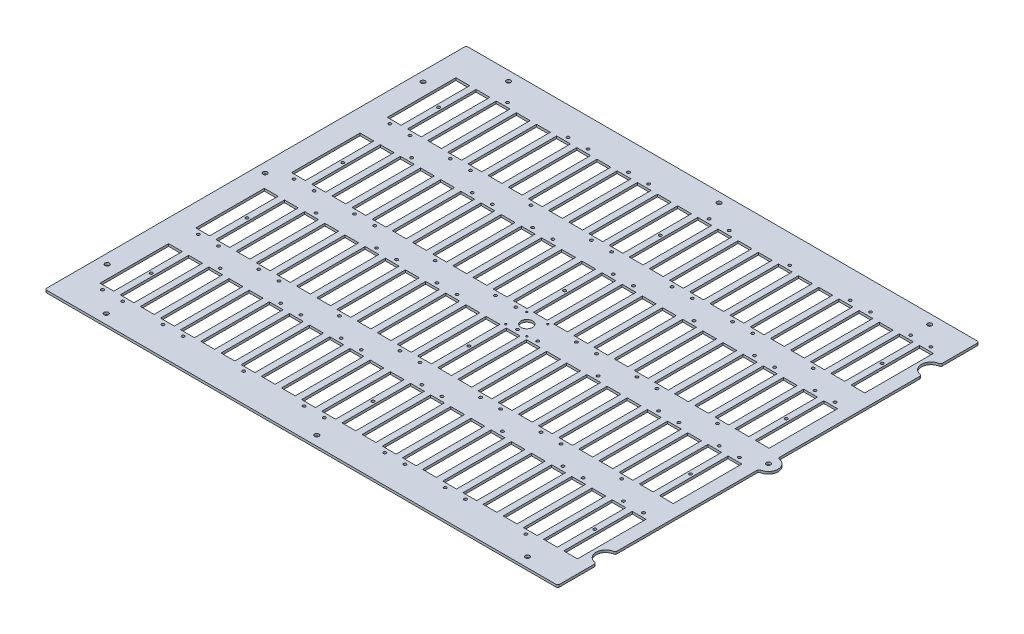
SolidWorks part; units mm, degrees
ref_plane "Front Plane" through (0, 0, 0) normal (0, 0, 1) x (1, 0, 0)
ref_plane "Top Plane" through (0, 0, 0) normal (0, 1, 0) x (1, 0, 0)
ref_plane "Right Plane" through (0, 0, 0) normal (1, 0, 0) x (0, 0, -1)
sketch "Sketch1" plane through (0, 0, 0) normal (0, 1, 0) x (1, 0, 0)
  line L0 (340.2584, 228.6) -> (340.2584, 279.5524)
  line L1 (-340.2584, -279.5524) -> (340.2584, -279.5524)
  line L2 (-340.2584, -279.5524) -> (-340.2584, 279.5524)
  line L3 (-340.2584, 279.5524) -> (340.2584, 279.5524)
  line L4 (340.2584, -279.5524) -> (340.2584, -228.6)
  line L5 (-340.2584, -279.5524) -> (340.2584, 279.5524) construction
  line L6 (-340.2584, 279.5524) -> (340.2584, -279.5524) construction
  line L7 (340.2584, 12.7) -> (340.2584, 203.2)
  line L8 (340.2584, -203.2) -> (340.2584, -12.7)
  arc A3 (340.2584, -203.2) -> (340.2584, -228.6) centre (340.2584, -215.9) ccw
  arc A4 (340.2584, -12.7) -> (340.2584, 12.7) centre (340.2584, 0) ccw
  arc A5 (340.2584, 228.6) -> (340.2584, 203.2) centre (340.2584, 215.9) ccw
  point P0 (0, 0)
  dimension "D3" = 25.4
  dimension "D1" = 559.1048
  dimension "D2" = 680.5168
extrude "Boss-Extrude1" add sketch "Sketch1" along normal blind 3.175
sketch "Sketch17" plane through (0, 3.175, 0) normal (0, 1, 0) x (1, 0, 0)
  line L0 (340.2584, 279.5524) -> (-340.2584, 279.5524) construction
  line L1 (-314.8584, 254.1524) -> (327.5584, 254.1524) construction
  line L2 (-314.8584, 254.1524) -> (-314.8584, -254.1524) construction
  line L3 (-314.8584, -254.1524) -> (327.5584, -254.1524) construction
  line L4 (327.5584, 254.1524) -> (327.5584, -254.1524) construction
  line L5 (-340.2584, 279.5524) -> (-340.2584, -279.5524) construction
  line L6 (-340.2584, -279.5524) -> (340.2584, -279.5524) construction
  line L7 (340.2584, -203.2) -> (340.2584, -12.7) construction
  line L8 (-283.8406, 236.1184) -> (-265.5526, 236.1184)
  line L9 (-310.5912, 236.1184) -> (-292.3032, 236.1184)
  line L10 (-310.5912, 236.1184) -> (-310.5912, 145.1864)
  line L11 (-310.5912, 145.1864) -> (-292.3032, 145.1864)
  line L12 (-292.3032, 236.1184) -> (-292.3032, 145.1864)
  line L13 (-283.8406, 236.1184) -> (-283.8406, 145.1864)
  line L14 (-265.5526, 236.1184) -> (-265.5526, 145.1864)
  line L15 (-283.8406, 145.1864) -> (-265.5526, 145.1864)
  line L16 (-257.09, 236.1184) -> (-238.802, 236.1184)
  line L17 (-257.09, 236.1184) -> (-257.09, 145.1864)
  line L18 (-238.802, 236.1184) -> (-238.802, 145.1864)
  line L19 (-257.09, 145.1864) -> (-238.802, 145.1864)
  line L20 (-230.3393, 236.1184) -> (-212.0513, 236.1184)
  line L21 (-230.3393, 236.1184) -> (-230.3393, 145.1864)
  line L22 (-212.0513, 236.1184) -> (-212.0513, 145.1864)
  line L23 (-230.3393, 145.1864) -> (-212.0513, 145.1864)
  line L24 (-203.5887, 236.1184) -> (-185.3007, 236.1184)
  line L25 (-203.5887, 236.1184) -> (-203.5887, 145.1864)
  line L26 (-185.3007, 236.1184) -> (-185.3007, 145.1864)
  line L27 (-203.5887, 145.1864) -> (-185.3007, 145.1864)
  line L28 (-176.8381, 236.1184) -> (-158.5501, 236.1184)
  line L29 (-176.8381, 236.1184) -> (-176.8381, 145.1864)
  line L30 (-158.5501, 236.1184) -> (-158.5501, 145.1864)
  line L31 (-176.8381, 145.1864) -> (-158.5501, 145.1864)
  line L32 (-150.0875, 236.1184) -> (-131.7995, 236.1184)
  line L33 (-150.0875, 236.1184) -> (-150.0875, 145.1864)
  line L34 (-131.7995, 236.1184) -> (-131.7995, 145.1864)
  line L35 (-150.0875, 145.1864) -> (-131.7995, 145.1864)
  line L36 (-123.3369, 236.1184) -> (-105.0489, 236.1184)
  line L37 (-123.3369, 236.1184) -> (-123.3369, 145.1864)
  line L38 (-105.0489, 236.1184) -> (-105.0489, 145.1864)
  line L39 (-123.3369, 145.1864) -> (-105.0489, 145.1864)
  line L40 (-96.5863, 236.1184) -> (-78.2983, 236.1184)
  line L41 (-96.5863, 236.1184) -> (-96.5863, 145.1864)
  line L42 (-78.2983, 236.1184) -> (-78.2983, 145.1864)
  line L43 (-96.5863, 145.1864) -> (-78.2983, 145.1864)
  line L44 (-69.8356, 236.1184) -> (-51.5476, 236.1184)
  line L45 (-69.8356, 236.1184) -> (-69.8356, 145.1864)
  line L46 (-51.5476, 236.1184) -> (-51.5476, 145.1864)
  line L47 (-69.8356, 145.1864) -> (-51.5476, 145.1864)
  line L48 (-43.085, 236.1184) -> (-24.797, 236.1184)
  line L49 (-43.085, 236.1184) -> (-43.085, 145.1864)
  line L50 (-24.797, 236.1184) -> (-24.797, 145.1864)
  line L51 (-43.085, 145.1864) -> (-24.797, 145.1864)
  line L52 (-16.3344, 236.1184) -> (1.9536, 236.1184)
  line L53 (-16.3344, 236.1184) -> (-16.3344, 145.1864)
  line L54 (1.9536, 236.1184) -> (1.9536, 145.1864)
  line L55 (-16.3344, 145.1864) -> (1.9536, 145.1864)
  line L56 (10.4162, 236.1184) -> (28.7042, 236.1184)
  line L57 (10.4162, 236.1184) -> (10.4162, 145.1864)
  line L58 (28.7042, 236.1184) -> (28.7042, 145.1864)
  line L59 (10.4162, 145.1864) -> (28.7042, 145.1864)
  line L60 (37.1668, 236.1184) -> (55.4548, 236.1184)
  line L61 (37.1668, 236.1184) -> (37.1668, 145.1864)
  line L62 (55.4548, 236.1184) -> (55.4548, 145.1864)
  line L63 (37.1668, 145.1864) -> (55.4548, 145.1864)
  line L64 (63.9174, 236.1184) -> (82.2054, 236.1184)
  line L65 (63.9174, 236.1184) -> (63.9174, 145.1864)
  line L66 (82.2054, 236.1184) -> (82.2054, 145.1864)
  line L67 (63.9174, 145.1864) -> (82.2054, 145.1864)
  line L68 (90.6681, 236.1184) -> (108.9561, 236.1184)
  line L69 (90.6681, 236.1184) -> (90.6681, 145.1864)
  line L70 (108.9561, 236.1184) -> (108.9561, 145.1864)
  line L71 (90.6681, 145.1864) -> (108.9561, 145.1864)
  line L72 (117.4187, 236.1184) -> (135.7067, 236.1184)
  line L73 (117.4187, 236.1184) -> (117.4187, 145.1864)
  line L74 (135.7067, 236.1184) -> (135.7067, 145.1864)
  line L75 (117.4187, 145.1864) -> (135.7067, 145.1864)
  line L76 (144.1693, 236.1184) -> (162.4573, 236.1184)
  line L77 (144.1693, 236.1184) -> (144.1693, 145.1864)
  line L78 (162.4573, 236.1184) -> (162.4573, 145.1864)
  line L79 (144.1693, 145.1864) -> (162.4573, 145.1864)
  line L80 (170.9199, 236.1184) -> (189.2079, 236.1184)
  line L81 (170.9199, 236.1184) -> (170.9199, 145.1864)
  line L82 (189.2079, 236.1184) -> (189.2079, 145.1864)
  line L83 (170.9199, 145.1864) -> (189.2079, 145.1864)
  line L84 (197.6705, 236.1184) -> (215.9585, 236.1184)
  line L85 (197.6705, 236.1184) -> (197.6705, 145.1864)
  line L86 (215.9585, 236.1184) -> (215.9585, 145.1864)
  line L87 (197.6705, 145.1864) -> (215.9585, 145.1864)
  line L88 (224.4211, 236.1184) -> (242.7091, 236.1184)
  line L89 (224.4211, 236.1184) -> (224.4211, 145.1864)
  line L90 (242.7091, 236.1184) -> (242.7091, 145.1864)
  line L91 (224.4211, 145.1864) -> (242.7091, 145.1864)
  line L92 (251.1718, 236.1184) -> (269.4598, 236.1184)
  line L93 (251.1718, 236.1184) -> (251.1718, 145.1864)
  line L94 (269.4598, 236.1184) -> (269.4598, 145.1864)
  line L95 (251.1718, 145.1864) -> (269.4598, 145.1864)
  line L96 (277.9224, 236.1184) -> (296.2104, 236.1184)
  line L97 (277.9224, 236.1184) -> (277.9224, 145.1864)
  line L98 (296.2104, 236.1184) -> (296.2104, 145.1864)
  line L99 (277.9224, 145.1864) -> (296.2104, 145.1864)
  line L100 (304.673, 236.1184) -> (322.961, 236.1184)
  line L101 (304.673, 236.1184) -> (304.673, 145.1864)
  line L102 (322.961, 236.1184) -> (322.961, 145.1864)
  line L103 (304.673, 145.1864) -> (322.961, 145.1864)
  line L104 (-283.8406, 109.0422) -> (-265.5526, 109.0422)
  line L105 (-283.8406, 109.0422) -> (-283.8406, 18.1102)
  line L106 (-265.5526, 109.0422) -> (-265.5526, 18.1102)
  line L107 (-283.8406, 18.1102) -> (-265.5526, 18.1102)
  line L108 (-257.09, 109.0422) -> (-238.802, 109.0422)
  line L109 (-257.09, 109.0422) -> (-257.09, 18.1102)
  line L110 (-238.802, 109.0422) -> (-238.802, 18.1102)
  line L111 (-257.09, 18.1102) -> (-238.802, 18.1102)
  line L112 (-230.3393, 109.0422) -> (-212.0513, 109.0422)
  line L113 (-230.3393, 109.0422) -> (-230.3393, 18.1102)
  line L114 (-212.0513, 109.0422) -> (-212.0513, 18.1102)
  line L115 (-230.3393, 18.1102) -> (-212.0513, 18.1102)
  line L116 (-203.5887, 109.0422) -> (-185.3007, 109.0422)
  line L117 (-203.5887, 109.0422) -> (-203.5887, 18.1102)
  line L118 (-185.3007, 109.0422) -> (-185.3007, 18.1102)
  line L119 (-203.5887, 18.1102) -> (-185.3007, 18.1102)
  line L120 (-176.8381, 109.0422) -> (-158.5501, 109.0422)
  line L121 (-176.8381, 109.0422) -> (-176.8381, 18.1102)
  line L122 (-158.5501, 109.0422) -> (-158.5501, 18.1102)
  line L123 (-176.8381, 18.1102) -> (-158.5501, 18.1102)
  line L124 (-150.0875, 109.0422) -> (-131.7995, 109.0422)
  line L125 (-150.0875, 109.0422) -> (-150.0875, 18.1102)
  line L126 (-131.7995, 109.0422) -> (-131.7995, 18.1102)
  line L127 (-150.0875, 18.1102) -> (-131.7995, 18.1102)
  line L128 (-123.3369, 109.0422) -> (-105.0489, 109.0422)
  line L129 (-123.3369, 109.0422) -> (-123.3369, 18.1102)
  line L130 (-105.0489, 109.0422) -> (-105.0489, 18.1102)
  line L131 (-123.3369, 18.1102) -> (-105.0489, 18.1102)
  line L132 (-96.5863, 109.0422) -> (-78.2983, 109.0422)
  line L133 (-96.5863, 109.0422) -> (-96.5863, 18.1102)
  line L134 (-78.2983, 109.0422) -> (-78.2983, 18.1102)
  line L135 (-96.5863, 18.1102) -> (-78.2983, 18.1102)
  line L136 (-69.8356, 109.0422) -> (-51.5476, 109.0422)
  line L137 (-69.8356, 109.0422) -> (-69.8356, 18.1102)
  line L138 (-51.5476, 109.0422) -> (-51.5476, 18.1102)
  line L139 (-69.8356, 18.1102) -> (-51.5476, 18.1102)
  line L140 (-43.085, 109.0422) -> (-24.797, 109.0422)
  line L141 (-43.085, 109.0422) -> (-43.085, 18.1102)
  line L142 (-24.797, 109.0422) -> (-24.797, 18.1102)
  line L143 (-43.085, 18.1102) -> (-24.797, 18.1102)
  line L144 (-16.3344, 109.0422) -> (1.9536, 109.0422)
  line L145 (-16.3344, 109.0422) -> (-16.3344, 18.1102)
  line L146 (1.9536, 109.0422) -> (1.9536, 18.1102)
  line L147 (-16.3344, 18.1102) -> (1.9536, 18.1102)
  line L148 (10.4162, 109.0422) -> (28.7042, 109.0422)
  line L149 (10.4162, 109.0422) -> (10.4162, 18.1102)
  line L150 (28.7042, 109.0422) -> (28.7042, 18.1102)
  line L151 (10.4162, 18.1102) -> (28.7042, 18.1102)
  line L152 (37.1668, 109.0422) -> (55.4548, 109.0422)
  line L153 (37.1668, 109.0422) -> (37.1668, 18.1102)
  line L154 (55.4548, 109.0422) -> (55.4548, 18.1102)
  line L155 (37.1668, 18.1102) -> (55.4548, 18.1102)
  line L156 (63.9174, 109.0422) -> (82.2054, 109.0422)
  line L157 (63.9174, 109.0422) -> (63.9174, 18.1102)
  line L158 (82.2054, 109.0422) -> (82.2054, 18.1102)
  line L159 (63.9174, 18.1102) -> (82.2054, 18.1102)
  line L160 (90.6681, 109.0422) -> (108.9561, 109.0422)
  line L161 (90.6681, 109.0422) -> (90.6681, 18.1102)
  line L162 (108.9561, 109.0422) -> (108.9561, 18.1102)
  line L163 (90.6681, 18.1102) -> (108.9561, 18.1102)
  line L164 (117.4187, 109.0422) -> (135.7067, 109.0422)
  line L165 (117.4187, 109.0422) -> (117.4187, 18.1102)
  line L166 (135.7067, 109.0422) -> (135.7067, 18.1102)
  line L167 (117.4187, 18.1102) -> (135.7067, 18.1102)
  line L168 (144.1693, 109.0422) -> (162.4573, 109.0422)
  line L169 (144.1693, 109.0422) -> (144.1693, 18.1102)
  line L170 (162.4573, 109.0422) -> (162.4573, 18.1102)
  line L171 (144.1693, 18.1102) -> (162.4573, 18.1102)
  line L172 (170.9199, 109.0422) -> (189.2079, 109.0422)
  line L173 (170.9199, 109.0422) -> (170.9199, 18.1102)
  line L174 (189.2079, 109.0422) -> (189.2079, 18.1102)
  line L175 (170.9199, 18.1102) -> (189.2079, 18.1102)
  line L176 (197.6705, 109.0422) -> (215.9585, 109.0422)
  line L177 (197.6705, 109.0422) -> (197.6705, 18.1102)
  line L178 (215.9585, 109.0422) -> (215.9585, 18.1102)
  line L179 (197.6705, 18.1102) -> (215.9585, 18.1102)
  line L180 (224.4211, 109.0422) -> (242.7091, 109.0422)
  line L181 (224.4211, 109.0422) -> (224.4211, 18.1102)
  line L182 (242.7091, 109.0422) -> (242.7091, 18.1102)
  line L183 (224.4211, 18.1102) -> (242.7091, 18.1102)
  line L184 (251.1718, 109.0422) -> (269.4598, 109.0422)
  line L185 (251.1718, 109.0422) -> (251.1718, 18.1102)
  line L186 (269.4598, 109.0422) -> (269.4598, 18.1102)
  line L187 (251.1718, 18.1102) -> (269.4598, 18.1102)
  line L188 (277.9224, 109.0422) -> (296.2104, 109.0422)
  line L189 (277.9224, 109.0422) -> (277.9224, 18.1102)
  line L190 (296.2104, 109.0422) -> (296.2104, 18.1102)
  line L191 (277.9224, 18.1102) -> (296.2104, 18.1102)
  line L192 (304.673, 109.0422) -> (322.961, 109.0422)
  line L193 (304.673, 109.0422) -> (304.673, 18.1102)
  line L194 (322.961, 109.0422) -> (322.961, 18.1102)
  line L195 (304.673, 18.1102) -> (322.961, 18.1102)
  line L196 (-283.8406, -18.034) -> (-265.5526, -18.034)
  line L197 (-283.8406, -18.034) -> (-283.8406, -108.966)
  line L198 (-265.5526, -18.034) -> (-265.5526, -108.966)
  line L199 (-283.8406, -108.966) -> (-265.5526, -108.966)
  line L200 (-257.09, -18.034) -> (-238.802, -18.034)
  line L201 (-257.09, -18.034) -> (-257.09, -108.966)
  line L202 (-238.802, -18.034) -> (-238.802, -108.966)
  line L203 (-257.09, -108.966) -> (-238.802, -108.966)
  line L204 (-230.3393, -18.034) -> (-212.0513, -18.034)
  line L205 (-230.3393, -18.034) -> (-230.3393, -108.966)
  line L206 (-212.0513, -18.034) -> (-212.0513, -108.966)
  line L207 (-230.3393, -108.966) -> (-212.0513, -108.966)
  line L208 (-203.5887, -18.034) -> (-185.3007, -18.034)
  line L209 (-203.5887, -18.034) -> (-203.5887, -108.966)
  line L210 (-185.3007, -18.034) -> (-185.3007, -108.966)
  line L211 (-203.5887, -108.966) -> (-185.3007, -108.966)
  line L212 (-176.8381, -18.034) -> (-158.5501, -18.034)
  line L213 (-176.8381, -18.034) -> (-176.8381, -108.966)
  line L214 (-158.5501, -18.034) -> (-158.5501, -108.966)
  line L215 (-176.8381, -108.966) -> (-158.5501, -108.966)
  line L216 (-150.0875, -18.034) -> (-131.7995, -18.034)
  line L217 (-150.0875, -18.034) -> (-150.0875, -108.966)
  line L218 (-131.7995, -18.034) -> (-131.7995, -108.966)
  line L219 (-150.0875, -108.966) -> (-131.7995, -108.966)
  line L220 (-123.3369, -18.034) -> (-105.0489, -18.034)
  line L221 (-123.3369, -18.034) -> (-123.3369, -108.966)
  line L222 (-105.0489, -18.034) -> (-105.0489, -108.966)
  line L223 (-123.3369, -108.966) -> (-105.0489, -108.966)
  line L224 (-96.5863, -18.034) -> (-78.2983, -18.034)
  line L225 (-96.5863, -18.034) -> (-96.5863, -108.966)
  line L226 (-78.2983, -18.034) -> (-78.2983, -108.966)
  line L227 (-96.5863, -108.966) -> (-78.2983, -108.966)
  line L228 (-69.8356, -18.034) -> (-51.5476, -18.034)
  line L229 (-69.8356, -18.034) -> (-69.8356, -108.966)
  line L230 (-51.5476, -18.034) -> (-51.5476, -108.966)
  line L231 (-69.8356, -108.966) -> (-51.5476, -108.966)
  line L232 (-43.085, -18.034) -> (-24.797, -18.034)
  line L233 (-43.085, -18.034) -> (-43.085, -108.966)
  line L234 (-24.797, -18.034) -> (-24.797, -108.966)
  line L235 (-43.085, -108.966) -> (-24.797, -108.966)
  line L236 (-16.3344, -18.034) -> (1.9536, -18.034)
  line L237 (-16.3344, -18.034) -> (-16.3344, -108.966)
  line L238 (1.9536, -18.034) -> (1.9536, -108.966)
  line L239 (-16.3344, -108.966) -> (1.9536, -108.966)
  line L240 (10.4162, -18.034) -> (28.7042, -18.034)
  line L241 (10.4162, -18.034) -> (10.4162, -108.966)
  line L242 (28.7042, -18.034) -> (28.7042, -108.966)
  line L243 (10.4162, -108.966) -> (28.7042, -108.966)
  line L244 (37.1668, -18.034) -> (55.4548, -18.034)
  line L245 (37.1668, -18.034) -> (37.1668, -108.966)
  line L246 (55.4548, -18.034) -> (55.4548, -108.966)
  line L247 (37.1668, -108.966) -> (55.4548, -108.966)
  line L248 (63.9174, -18.034) -> (82.2054, -18.034)
  line L249 (63.9174, -18.034) -> (63.9174, -108.966)
  line L250 (82.2054, -18.034) -> (82.2054, -108.966)
  line L251 (63.9174, -108.966) -> (82.2054, -108.966)
  line L252 (90.6681, -18.034) -> (108.9561, -18.034)
  line L253 (90.6681, -18.034) -> (90.6681, -108.966)
  line L254 (108.9561, -18.034) -> (108.9561, -108.966)
  line L255 (90.6681, -108.966) -> (108.9561, -108.966)
  line L256 (117.4187, -18.034) -> (135.7067, -18.034)
  line L257 (117.4187, -18.034) -> (117.4187, -108.966)
  line L258 (135.7067, -18.034) -> (135.7067, -108.966)
  line L259 (117.4187, -108.966) -> (135.7067, -108.966)
  line L260 (144.1693, -18.034) -> (162.4573, -18.034)
  line L261 (144.1693, -18.034) -> (144.1693, -108.966)
  line L262 (162.4573, -18.034) -> (162.4573, -108.966)
  line L263 (144.1693, -108.966) -> (162.4573, -108.966)
  line L264 (170.9199, -18.034) -> (189.2079, -18.034)
  line L265 (170.9199, -18.034) -> (170.9199, -108.966)
  line L266 (189.2079, -18.034) -> (189.2079, -108.966)
  line L267 (170.9199, -108.966) -> (189.2079, -108.966)
  line L268 (197.6705, -18.034) -> (215.9585, -18.034)
  line L269 (197.6705, -18.034) -> (197.6705, -108.966)
  line L270 (215.9585, -18.034) -> (215.9585, -108.966)
  line L271 (197.6705, -108.966) -> (215.9585, -108.966)
  line L272 (224.4211, -18.034) -> (242.7091, -18.034)
  line L273 (224.4211, -18.034) -> (224.4211, -108.966)
  line L274 (242.7091, -18.034) -> (242.7091, -108.966)
  line L275 (224.4211, -108.966) -> (242.7091, -108.966)
  line L276 (251.1718, -18.034) -> (269.4598, -18.034)
  line L277 (251.1718, -18.034) -> (251.1718, -108.966)
  line L278 (269.4598, -18.034) -> (269.4598, -108.966)
  line L279 (251.1718, -108.966) -> (269.4598, -108.966)
  line L280 (277.9224, -18.034) -> (296.2104, -18.034)
  line L281 (277.9224, -18.034) -> (277.9224, -108.966)
  line L282 (296.2104, -18.034) -> (296.2104, -108.966)
  line L283 (277.9224, -108.966) -> (296.2104, -108.966)
  line L284 (304.673, -18.034) -> (322.961, -18.034)
  line L285 (304.673, -18.034) -> (304.673, -108.966)
  line L286 (322.961, -18.034) -> (322.961, -108.966)
  line L287 (304.673, -108.966) -> (322.961, -108.966)
  line L288 (-283.8406, -145.1102) -> (-265.5526, -145.1102)
  line L289 (-283.8406, -145.1102) -> (-283.8406, -236.0422)
  line L290 (-265.5526, -145.1102) -> (-265.5526, -236.0422)
  line L291 (-283.8406, -236.0422) -> (-265.5526, -236.0422)
  line L292 (-257.09, -145.1102) -> (-238.802, -145.1102)
  line L293 (-257.09, -145.1102) -> (-257.09, -236.0422)
  line L294 (-238.802, -145.1102) -> (-238.802, -236.0422)
  line L295 (-257.09, -236.0422) -> (-238.802, -236.0422)
  line L296 (-230.3393, -145.1102) -> (-212.0513, -145.1102)
  line L297 (-230.3393, -145.1102) -> (-230.3393, -236.0422)
  line L298 (-212.0513, -145.1102) -> (-212.0513, -236.0422)
  line L299 (-230.3393, -236.0422) -> (-212.0513, -236.0422)
  line L300 (-203.5887, -145.1102) -> (-185.3007, -145.1102)
  line L301 (-203.5887, -145.1102) -> (-203.5887, -236.0422)
  line L302 (-185.3007, -145.1102) -> (-185.3007, -236.0422)
  line L303 (-203.5887, -236.0422) -> (-185.3007, -236.0422)
  line L304 (-176.8381, -145.1102) -> (-158.5501, -145.1102)
  line L305 (-176.8381, -145.1102) -> (-176.8381, -236.0422)
  line L306 (-158.5501, -145.1102) -> (-158.5501, -236.0422)
  line L307 (-176.8381, -236.0422) -> (-158.5501, -236.0422)
  line L308 (-150.0875, -145.1102) -> (-131.7995, -145.1102)
  line L309 (-150.0875, -145.1102) -> (-150.0875, -236.0422)
  line L310 (-131.7995, -145.1102) -> (-131.7995, -236.0422)
  line L311 (-150.0875, -236.0422) -> (-131.7995, -236.0422)
  line L312 (-123.3369, -145.1102) -> (-105.0489, -145.1102)
  line L313 (-123.3369, -145.1102) -> (-123.3369, -236.0422)
  line L314 (-105.0489, -145.1102) -> (-105.0489, -236.0422)
  line L315 (-123.3369, -236.0422) -> (-105.0489, -236.0422)
  line L316 (-96.5863, -145.1102) -> (-78.2983, -145.1102)
  line L317 (-96.5863, -145.1102) -> (-96.5863, -236.0422)
  line L318 (-78.2983, -145.1102) -> (-78.2983, -236.0422)
  line L319 (-96.5863, -236.0422) -> (-78.2983, -236.0422)
  line L320 (-69.8356, -145.1102) -> (-51.5476, -145.1102)
  line L321 (-69.8356, -145.1102) -> (-69.8356, -236.0422)
  line L322 (-51.5476, -145.1102) -> (-51.5476, -236.0422)
  line L323 (-69.8356, -236.0422) -> (-51.5476, -236.0422)
  line L324 (-43.085, -145.1102) -> (-24.797, -145.1102)
  line L325 (-43.085, -145.1102) -> (-43.085, -236.0422)
  line L326 (-24.797, -145.1102) -> (-24.797, -236.0422)
  line L327 (-43.085, -236.0422) -> (-24.797, -236.0422)
  line L328 (-16.3344, -145.1102) -> (1.9536, -145.1102)
  line L329 (-16.3344, -145.1102) -> (-16.3344, -236.0422)
  line L330 (1.9536, -145.1102) -> (1.9536, -236.0422)
  line L331 (-16.3344, -236.0422) -> (1.9536, -236.0422)
  line L332 (10.4162, -145.1102) -> (28.7042, -145.1102)
  line L333 (10.4162, -145.1102) -> (10.4162, -236.0422)
  line L334 (28.7042, -145.1102) -> (28.7042, -236.0422)
  line L335 (10.4162, -236.0422) -> (28.7042, -236.0422)
  line L336 (37.1668, -145.1102) -> (55.4548, -145.1102)
  line L337 (37.1668, -145.1102) -> (37.1668, -236.0422)
  line L338 (55.4548, -145.1102) -> (55.4548, -236.0422)
  line L339 (37.1668, -236.0422) -> (55.4548, -236.0422)
  line L340 (63.9174, -145.1102) -> (82.2054, -145.1102)
  line L341 (63.9174, -145.1102) -> (63.9174, -236.0422)
  line L342 (82.2054, -145.1102) -> (82.2054, -236.0422)
  line L343 (63.9174, -236.0422) -> (82.2054, -236.0422)
  line L344 (90.6681, -145.1102) -> (108.9561, -145.1102)
  line L345 (90.6681, -145.1102) -> (90.6681, -236.0422)
  line L346 (108.9561, -145.1102) -> (108.9561, -236.0422)
  line L347 (90.6681, -236.0422) -> (108.9561, -236.0422)
  line L348 (117.4187, -145.1102) -> (135.7067, -145.1102)
  line L349 (117.4187, -145.1102) -> (117.4187, -236.0422)
  line L350 (135.7067, -145.1102) -> (135.7067, -236.0422)
  line L351 (117.4187, -236.0422) -> (135.7067, -236.0422)
  line L352 (144.1693, -145.1102) -> (162.4573, -145.1102)
  line L353 (144.1693, -145.1102) -> (144.1693, -236.0422)
  line L354 (162.4573, -145.1102) -> (162.4573, -236.0422)
  line L355 (144.1693, -236.0422) -> (162.4573, -236.0422)
  line L356 (170.9199, -145.1102) -> (189.2079, -145.1102)
  line L357 (170.9199, -145.1102) -> (170.9199, -236.0422)
  line L358 (189.2079, -145.1102) -> (189.2079, -236.0422)
  line L359 (170.9199, -236.0422) -> (189.2079, -236.0422)
  line L360 (197.6705, -145.1102) -> (215.9585, -145.1102)
  line L361 (197.6705, -145.1102) -> (197.6705, -236.0422)
  line L362 (215.9585, -145.1102) -> (215.9585, -236.0422)
  line L363 (197.6705, -236.0422) -> (215.9585, -236.0422)
  line L364 (224.4211, -145.1102) -> (242.7091, -145.1102)
  line L365 (224.4211, -145.1102) -> (224.4211, -236.0422)
  line L366 (242.7091, -145.1102) -> (242.7091, -236.0422)
  line L367 (224.4211, -236.0422) -> (242.7091, -236.0422)
  line L368 (251.1718, -145.1102) -> (269.4598, -145.1102)
  line L369 (251.1718, -145.1102) -> (251.1718, -236.0422)
  line L370 (269.4598, -145.1102) -> (269.4598, -236.0422)
  line L371 (251.1718, -236.0422) -> (269.4598, -236.0422)
  line L372 (277.9224, -145.1102) -> (296.2104, -145.1102)
  line L373 (277.9224, -145.1102) -> (277.9224, -236.0422)
  line L374 (296.2104, -145.1102) -> (296.2104, -236.0422)
  line L375 (277.9224, -236.0422) -> (296.2104, -236.0422)
  line L376 (304.673, -145.1102) -> (322.961, -145.1102)
  line L377 (304.673, -145.1102) -> (304.673, -236.0422)
  line L378 (322.961, -145.1102) -> (322.961, -236.0422)
  line L379 (304.673, -236.0422) -> (322.961, -236.0422)
  line L380 (-310.5912, 109.0422) -> (-292.3032, 109.0422)
  line L381 (-310.5912, 109.0422) -> (-310.5912, 18.1102)
  line L382 (-292.3032, 109.0422) -> (-292.3032, 18.1102)
  line L383 (-310.5912, 18.1102) -> (-292.3032, 18.1102)
  line L384 (-310.5912, -18.034) -> (-292.3032, -18.034)
  line L385 (-310.5912, -18.034) -> (-310.5912, -108.966)
  line L386 (-292.3032, -18.034) -> (-292.3032, -108.966)
  line L387 (-310.5912, -108.966) -> (-292.3032, -108.966)
  line L388 (-310.5912, -145.1102) -> (-292.3032, -145.1102)
  line L389 (-310.5912, -145.1102) -> (-310.5912, -236.0422)
  line L390 (-292.3032, -145.1102) -> (-292.3032, -236.0422)
  line L391 (-310.5912, -236.0422) -> (-292.3032, -236.0422)
  line L392 (340.2584, -279.5524) -> (340.2584, -228.6) construction
  dimension "D1" = 25.4
  dimension "D2" = 25.4
  dimension "D3" = 25.4
  dimension "D4" = 12.7
  dimension "D5" = 18.288
  dimension "D6" = 90.932
  dimension "D7" = 4.2672
  dimension "D8" = 18.034
  dimension "D9" = 508.3048
  dimension "D10" = 642.4168
  dimension "D11" = 24
  dimension "D13" = 17.2974
  dimension "D14" = 43.5102
  dimension "D12" = 4
extrude "Cut-Extrude5" cut sketch "Sketch17" against normal through all
hole_wizard "#25 (0.1495) Diameter Hole1" positions "Sketch18" profile "Sketch19" hole size "#25" standard "ANSI Inch" end condition through all
sketch "Sketch18" plane through (0, 3.175, 0) normal (0, 1, 0) x (1, 0, 0)
  line L19 (340.2584, -241.8842) -> (-340.2584, -241.8842) construction
  line L20 (340.2584, -279.5524) -> (340.2584, -228.6) construction
  line L21 (-340.2584, 279.5524) -> (-340.2584, -279.5524) construction
  line L22 (340.2584, -139.2682) -> (-340.2584, -139.2682) construction
  line L23 (340.2584, -203.2) -> (340.2584, -12.7) construction
  line L24 (313.817, -236.0422) -> (313.817, -254.0762) construction
  line L25 (304.673, -236.0422) -> (322.961, -236.0422) construction
  line L29 (322.961, -145.1102) -> (304.673, -145.1102) construction
  line L30 (313.817, -241.8842) -> (313.817, -139.2682) construction
  line L32 (287.0664, -241.8842) -> (287.0664, -139.2682) construction
  line L33 (260.3158, -241.8842) -> (260.3158, -139.2682) construction
  line L34 (233.5651, -241.8842) -> (233.5651, -139.2682) construction
  line L35 (206.8145, -241.8842) -> (206.8145, -139.2682) construction
  line L36 (180.0639, -241.8842) -> (180.0639, -139.2682) construction
  line L37 (153.3133, -241.8842) -> (153.3133, -139.2682) construction
  line L38 (126.5627, -241.8842) -> (126.5627, -139.2682) construction
  line L39 (99.8121, -241.8842) -> (99.8121, -139.2682) construction
  line L40 (73.0614, -241.8842) -> (73.0614, -139.2682) construction
  line L41 (46.3108, -241.8842) -> (46.3108, -139.2682) construction
  line L42 (19.5602, -241.8842) -> (19.5602, -139.2682) construction
  line L43 (-7.1904, -241.8842) -> (-7.1904, -139.2682) construction
  line L44 (-33.941, -241.8842) -> (-33.941, -139.2682) construction
  line L45 (-60.6916, -241.8842) -> (-60.6916, -139.2682) construction
  line L46 (-87.4423, -241.8842) -> (-87.4423, -139.2682) construction
  line L47 (-114.1929, -241.8842) -> (-114.1929, -139.2682) construction
  line L48 (-140.9435, -241.8842) -> (-140.9435, -139.2682) construction
  line L49 (-167.6941, -241.8842) -> (-167.6941, -139.2682) construction
  line L50 (-194.4447, -241.8842) -> (-194.4447, -139.2682) construction
  line L51 (-221.1953, -241.8842) -> (-221.1953, -139.2682) construction
  line L52 (-247.946, -241.8842) -> (-247.946, -139.2682) construction
  line L53 (-274.6966, -241.8842) -> (-274.6966, -139.2682) construction
  line L54 (-301.4472, -241.8842) -> (-301.4472, -139.2682) construction
  point P472 (313.817, -139.2682)
  point P477 (287.0664, -139.2682)
  point P478 (260.3158, -241.8842)
  point P481 (233.5651, -139.2682)
  point P483 (206.8145, -139.2682)
  point P484 (180.0639, -241.8842)
  point P486 (153.3133, -241.8842)
  point P489 (126.5627, -139.2682)
  point P490 (99.8121, -241.8842)
  point P492 (73.0614, -241.8842)
  point P495 (46.3108, -139.2682)
  point P497 (19.5602, -139.2682)
  point P498 (-7.1904, -241.8842)
  point P500 (-33.941, -241.8842)
  point P503 (-60.6916, -139.2682)
  point P505 (-87.4423, -139.2682)
  point P506 (-114.1929, -241.8842)
  point P509 (-140.9435, -139.2682)
  point P511 (-167.6941, -139.2682)
  point P512 (-194.4447, -241.8842)
  point P514 (-221.1953, -241.8842)
  point P517 (-247.946, -139.2682)
  point P518 (-274.6966, -241.8842)
  point P520 (-301.4472, -241.8842)
  point P575 (313.817, -12.192)
  point P576 (287.0664, -12.192)
  point P577 (260.3158, -114.808)
  point P578 (233.5651, -12.192)
  point P579 (206.8145, -12.192)
  point P580 (180.0639, -114.808)
  point P581 (153.3133, -114.808)
  point P582 (126.5627, -12.192)
  point P583 (99.8121, -114.808)
  point P584 (73.0614, -114.808)
  point P585 (46.3108, -12.192)
  point P586 (19.5602, -12.192)
  point P587 (-7.1904, -114.808)
  point P588 (-33.941, -114.808)
  point P589 (-60.6916, -12.192)
  point P590 (-87.4423, -12.192)
  point P591 (-114.1929, -114.808)
  point P592 (-140.9435, -12.192)
  point P593 (-167.6941, -12.192)
  point P594 (-194.4447, -114.808)
  point P595 (-221.1953, -114.808)
  point P596 (-247.946, -12.192)
  point P597 (-274.6966, -114.808)
  point P598 (-301.4472, -114.808)
  point P599 (313.817, 114.8842)
  point P600 (287.0664, 114.8842)
  point P601 (260.3158, 12.2682)
  point P602 (233.5651, 114.8842)
  point P603 (206.8145, 114.8842)
  point P604 (180.0639, 12.2682)
  point P605 (153.3133, 12.2682)
  point P606 (126.5627, 114.8842)
  point P607 (99.8121, 12.2682)
  point P608 (73.0614, 12.2682)
  point P609 (46.3108, 114.8842)
  point P610 (19.5602, 114.8842)
  point P611 (-7.1904, 12.2682)
  point P612 (-33.941, 12.2682)
  point P613 (-60.6916, 114.8842)
  point P614 (-87.4423, 114.8842)
  point P615 (-114.1929, 12.2682)
  point P616 (-140.9435, 114.8842)
  point P617 (-167.6941, 114.8842)
  point P618 (-194.4447, 12.2682)
  point P619 (-221.1953, 12.2682)
  point P620 (-247.946, 114.8842)
  point P621 (-274.6966, 12.2682)
  point P622 (-301.4472, 12.2682)
  point P623 (313.817, 241.9604)
  point P624 (287.0664, 241.9604)
  point P625 (260.3158, 139.3444)
  point P626 (233.5651, 241.9604)
  point P627 (206.8145, 241.9604)
  point P628 (180.0639, 139.3444)
  point P629 (153.3133, 139.3444)
  point P630 (126.5627, 241.9604)
  point P631 (99.8121, 139.3444)
  point P632 (73.0614, 139.3444)
  point P633 (46.3108, 241.9604)
  point P634 (19.5602, 241.9604)
  point P635 (-7.1904, 139.3444)
  point P636 (-33.941, 139.3444)
  point P637 (-60.6916, 241.9604)
  point P638 (-87.4423, 241.9604)
  point P639 (-114.1929, 139.3444)
  point P640 (-140.9435, 241.9604)
  point P641 (-167.6941, 241.9604)
  point P642 (-194.4447, 139.3444)
  point P643 (-221.1953, 139.3444)
  point P644 (-247.946, 241.9604)
  point P645 (-274.6966, 139.3444)
  point P646 (-301.4472, 139.3444)
  dimension "D1" = 5.842
  dimension "D2" = 5.842
  dimension "D3" = 24
  dimension "D4" = 4
sketch "Sketch19" plane through (-301.4472, 3.175, -139.3444) normal (1, 0, 0) x (0, 0, 1)
  line L0 (0, 0) -> (0, 3.175)
  line L1 (0, 3.175) -> (1.8986, 3.175)
  line L2 (1.8986, 3.175) -> (1.8986, 0)
  line L5 (1.8986, 0) -> (0, 0)
  line L11 (0, -6.35) -> (0, 107.95) construction
  dimension "Thru Hole Dia." = 3.7973
  dimension "Thru Hole Depth" = 3.175
fillet "Fillet1" radius 2.54 10 edges at (-340.2584, 1.5875, -279.5524) (-340.2584, 1.5875, 279.5524) (340.2584, 1.5875, 279.5524) (340.2584, 1.5875, 228.6) (340.2584, 1.5875, 203.2) (340.2584, 1.5875, 12.7) (340.2584, 1.5875, -12.7) (340.2584, 1.5875, -203.2) (340.2584, 1.5875, -279.5524) (340.2584, 1.5875, -228.6)
hole_wizard "#6 Clearance Hole1" positions "Sketch8" profile "Sketch9" hole size "#6" standard "ANSI Inch" end condition through all
sketch "Sketch8" plane through (0, 3.175, 0) normal (0, 1, 0) x (1, 0, 0)
  line L13 (-292.3032, 236.1184) -> (-283.8406, 145.1864) construction
  line L15 (1.9536, 236.1184) -> (10.4162, 145.1864) construction
  line L17 (296.2104, 236.1184) -> (304.673, 145.1864) construction
  line L18 (-292.3032, 109.0422) -> (-283.8406, 18.1102) construction
  line L19 (1.9536, 109.0422) -> (10.4162, 18.1102) construction
  line L20 (296.2104, 109.0422) -> (304.673, 18.1102) construction
  line L21 (-292.3032, -18.034) -> (-283.8406, -108.966) construction
  line L22 (1.9536, -18.034) -> (10.4162, -108.966) construction
  line L23 (296.2104, -18.034) -> (304.673, -108.966) construction
  line L24 (-292.3032, -145.1102) -> (-283.8406, -236.0422) construction
  line L25 (1.9536, -145.1102) -> (10.4162, -236.0422) construction
  line L26 (296.2104, -145.1102) -> (304.673, -236.0422) construction
  point P129 (-288.0719, 190.6524)
  point P131 (6.1849, 190.6524)
  point P133 (300.4417, 190.6524)
  point P146 (-288.0719, 63.5762)
  point P147 (6.1849, 63.5762)
  point P148 (300.4417, 63.5762)
  point P155 (-288.0719, -63.5)
  point P156 (6.1849, -63.5)
  point P157 (300.4417, -63.5)
  point P164 (-288.0719, -190.5762)
  point P165 (6.1849, -190.5762)
  point P166 (300.4417, -190.5762)
  dimension "D1" = 4
sketch "Sketch9" plane through (300.4417, 3.175, 190.5762) normal (1, 0, 0) x (0, 0, 1)
  line L0 (0, 0) -> (0, 3.175)
  line L1 (0, 3.175) -> (1.8986, 3.175)
  line L2 (1.8986, 3.175) -> (1.8986, 0)
  line L5 (1.8986, 0) -> (0, 0)
  line L11 (0, -6.35) -> (0, 107.95) construction
  dimension "Thru Hole Dia." = 3.7973
  dimension "Thru Hole Depth" = 3.175
hole_wizard "#2 Clearance Hole1" positions "Sketch13" profile "Sketch14" hole size "#2" standard "ANSI Inch" end condition through all
sketch "Sketch13" plane through (0, 3.175, 0) normal (0, 1, 0) x (1, 0, 0)
  line L9 (322.961, -108.966) -> (322.961, -18.034) construction
  line L10 (322.961, -18.034) -> (304.673, -18.034) construction
  line L18 (10.4162, 18.1102) -> (28.7042, -18.034) construction
  line L21 (5.6261, -13.9319) -> (33.5661, -13.9319) construction
  line L22 (5.6261, -13.9319) -> (5.6261, 14.0081) construction
  line L23 (5.6261, 14.0081) -> (33.5661, 14.0081) construction
  line L24 (33.5661, -13.9319) -> (33.5661, 14.0081) construction
  line L25 (5.6261, -13.9319) -> (33.5661, 14.0081) construction
  line L26 (5.6261, 14.0081) -> (33.5661, -13.9319) construction
  line L27 (10.4162, 18.1102) -> (28.7042, 18.1102) construction
  point P129 (5.6261, 14.0081)
  point P132 (5.6261, -13.9319)
  point P135 (33.5661, -13.9319)
  point P138 (33.5661, 14.0081)
  dimension "D1" = 27.94
  dimension "D2" = 27.94
  dimension "D3" = 4.1021
sketch "Sketch14" plane through (33.5661, 3.175, -14.0081) normal (1, 0, 0) x (0, 0, 1)
  line L0 (0, 0) -> (0, 3.175)
  line L1 (0, 3.175) -> (1.2192, 3.175)
  line L2 (1.2192, 3.175) -> (1.2192, 0)
  line L5 (1.2192, 0) -> (0, 0)
  line L11 (0, -6.35) -> (0, 107.95) construction
  dimension "Thru Hole Dia." = 2.4384
  dimension "Thru Hole Depth" = 3.175
sketch "Sketch20" plane through (0, 3.175, 0) normal (0, 1, 0) x (1, 0, 0)
  line L0 (5.6261, 14.0081) -> (33.5661, -13.9319) construction
  circle A0 centre (19.5961, 0.0381) radius 7.62
  dimension "D1" = 15.24
extrude "Cut-Extrude6" cut sketch "Sketch20" against normal through all
hole_wizard "#1 (0.228) Diameter Hole1" positions "Sketch21" profile "Sketch22" hole size "#1" standard "ANSI Inch" end condition through all
sketch "Sketch21" plane through (0, 3.175, 0) normal (0, 1, 0) x (1, 0, 0)
  point P0 (287.274, -266.8524)
  point P12 (287.274, 266.8524)
  point P15 (7.874, 266.8524)
  point P18 (-271.526, 266.8524)
  point P21 (-327.5584, 209.55)
  point P24 (-327.5584, 0)
  point P27 (-327.5584, -209.55)
  point P30 (-271.526, -266.8524)
  point P33 (7.874, -266.8524)
  point P41 (340.2584, 0)
sketch "Sketch22" plane through (287.274, 3.175, 266.8524) normal (1, 0, 0) x (0, 0, 1)
  line L0 (0, 0) -> (0, 3.175)
  line L1 (0, 3.175) -> (2.8956, 3.175)
  line L2 (2.8956, 3.175) -> (2.8956, 0)
  line L5 (2.8956, 0) -> (0, 0)
  line L11 (0, -6.35) -> (0, 107.95) construction
  dimension "Thru Hole Dia." = 5.7912
  dimension "Thru Hole Depth" = 3.175
